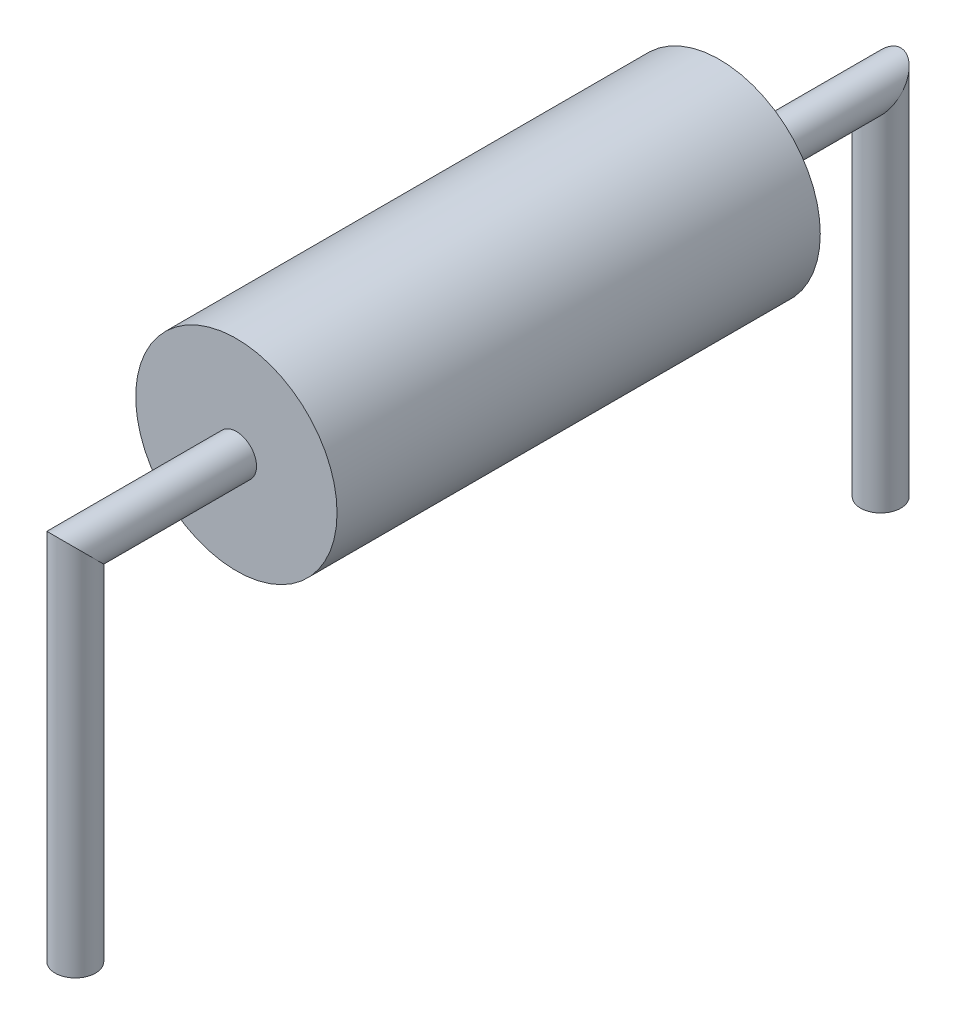
SolidWorks part; units mm, degrees
ref_plane "Front Plane" through (0, 0, 0) normal (0, 0, 1) x (1, 0, 0)
ref_plane "Top Plane" through (0, 0, 0) normal (0, 1, 0) x (1, 0, 0)
ref_plane "Right Plane" through (0, 0, 0) normal (1, 0, 0) x (0, 0, -1)
sketch "Sketch1" plane through (0, 0, 0) normal (0, 0, 1) x (1, 0, 0)
  circle A0 centre (0, 1.25) radius 1.25
  dimension "D1" = 2.5
extrude "Boss-Extrude1" add sketch "Sketch1" along normal mid plane 6
sketch "Sketch2" plane through (0, 0, 3) normal (0, 0, 1) x (1, 0, 0)
  circle A0 centre (0, 1.25) radius 0.25
  dimension "D1" = 0.5
extrude "Boss-Extrude2" add sketch "Sketch2" along normal blind 2.25 and the other way blind 8.25
sketch "Sketch3" plane through (0, 0, 0) normal (0, 1, 0) x (1, 0, 0)
  line L0 (0.25, 3) -> (0.25, 5.25) construction
  line L1 (-0.25, 5.25) -> (-0.25, 3) construction
  line L2 (0.25, 5.25) -> (-0.25, 5.25) construction
  line L3 (0.25, -5.25) -> (0.25, -3) construction
  line L4 (-0.25, -3) -> (-0.25, -5.25) construction
  line L5 (-0.25, -5.25) -> (0.25, -5.25) construction
  circle A0 centre (0, -5) radius 0.25
  circle A1 centre (0, 5) radius 0.25
extrude "Boss-Extrude3" add sketch "Sketch3" along normal up to next and the other way blind 3.2
sketch "Sketch4" plane through (0, -3.2, 0) normal (0, -1, 0) x (-1, 0, 0)
  line L0 (0.25, -5) -> (0.35, -5)
  line L1 (0.35, -5) -> (0.35, -5.35)
  line L2 (0.35, -5.35) -> (-0.35, -5.35)
  line L3 (-0.35, -5.35) -> (-0.35, -5)
  line L4 (-0.35, -5) -> (-0.25, -5)
  line L5 (-0.25, 5) -> (-0.35, 5)
  line L6 (-0.35, 5) -> (-0.35, 5.35)
  line L7 (-0.35, 5.35) -> (0.35, 5.35)
  line L8 (0.35, 5.35) -> (0.35, 5)
  line L9 (0.35, 5) -> (0.25, 5)
  arc A0 (-0.25, -5) -> (0.25, -5) centre (0, -5) ccw
  circle A1 centre (0, -5) radius 0.25 construction
  arc A2 (0.25, 5) -> (-0.25, 5) centre (0, 5) ccw
  circle A3 centre (0, 5) radius 0.25 construction
  point P1 (0, -5.25)
  point P5 (0, -5.35)
  point P22 (0, 5.35)
  dimension "D1" = 0.7
  dimension "D2" = 0.35
  dimension "D3" = 0.35
  dimension "D4" = 0.7
extrude "Cut-Extrude1" cut sketch "Sketch4" against normal through all
